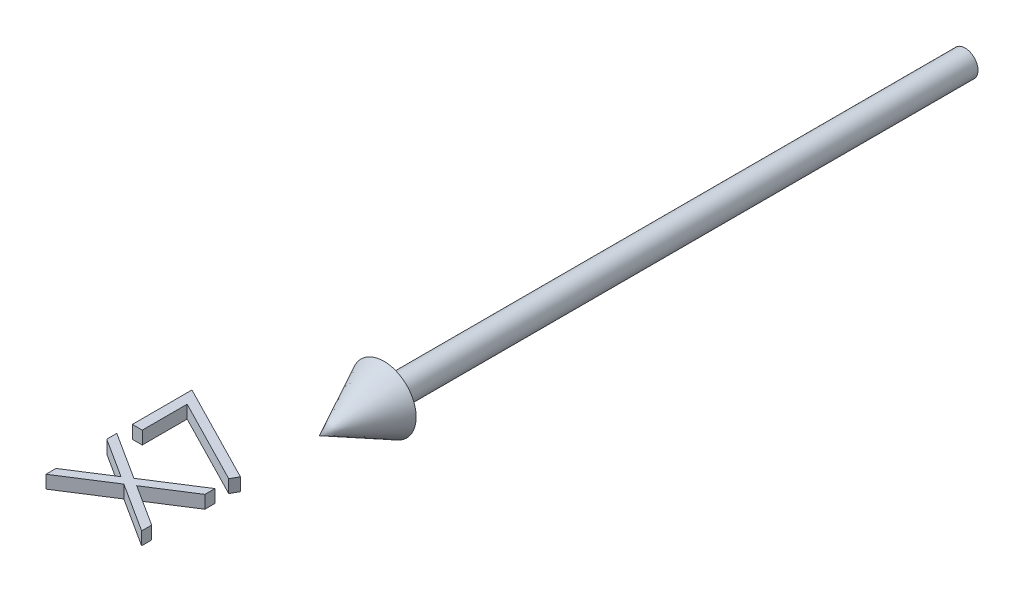
SolidWorks part; units mm, degrees
ref_plane "Front Plane" through (0, 0, 0) normal (0, 0, 1) x (1, 0, 0)
ref_plane "Top Plane" through (0, 0, 0) normal (0, 1, 0) x (1, 0, 0)
ref_plane "Right Plane" through (0, 0, 0) normal (1, 0, 0) x (0, 0, -1)
sketch "Sketch2" plane through (0, 0, 0) normal (0, 1, 0) x (1, 0, 0)
  line L0 (0, 41.95) -> (0, -114.4521) construction
  line L1 (-36.8894, 0) -> (41.4965, 0) construction
  line L2 (0, -100) -> (5, -90)
  line L3 (5, -90) -> (2, -90)
  line L4 (2, -90) -> (2, 0)
  line L5 (2, 0) -> (0, 0)
  line L6 (0, 0) -> (0, -100)
  dimension "D1" = 100
  dimension "D2" = 2
  dimension "D3" = 10
  dimension "D4" = 5
revolve "Revolve1" add sketch "Sketch2" angle 360 about L0
sketch "Sketch3" plane through (0, 0, 0) normal (0, 1, 0) x (1, 0, 0)
  line L0 (0, -103.9528) -> (0, -147.2622) construction
  line L1 (-18.6107, -118.3811) -> (18.3141, -118.3811) construction
  text T0 "X7\r\n\r\n\r\n" font "Century Gothic" height 15
extrude "Boss-Extrude1" add sketch "Sketch3" against normal blind 1 and the other way blind 1 separate body
equation "\"frame_arrow_length\"=100"
equation "\"D1@Sketch2\"=\"frame_arrow_length\""
equation "\"frame_arrow_odA\"=4"
equation "\"D2@Sketch2\"=\"frame_arrow_odA\"/2"
equation "\"frame_arrow_head_od\"=5"
equation "\"D4@Sketch2\"=\"frame_arrow_head_od\""
equation "\"frame_arrow_head_length\"=10"
equation "\"D3@Sketch2\"=\"frame_arrow_head_length\""
equation "\"tvarobot_theta1\"=30"
equation "\"link0_ringA_odA\"= 40"
equation "\"link0_ringA_odB\"= 25"
equation "\"link0_ringA_id\"= 20"
equation "\"link0_ringA_thickness\"= (\"link0_ringA_odB\" - \"link0_ringA_id\")/2"
equation "\"link0_ringA_height\"= 3"
equation "\"link0_ringA_heightA\"= 1.5"
equation "\"link0_ringA_heightB\"=\"link0_ringA_height\"-\"link0_ringA_heightA\""
equation "\"link0_ringB_odA\"= 40"
equation "\"link0_ringB_odB\"= 29"
equation "\"link0_ringB_id\"= \"link0_shaftA_bearing_id\"+1"
equation "\"link0_ringB_thickness\"= (\"link0_ringB_odB\" - \"link0_ringB_id\")/2"
equation "\"link0_ringB_height\"= 3"
equation "\"link0_ringB_heightA\"= 1.5"
equation "\"link0_ringB_heightB\"=\"link0_ringB_height\"-\"link0_ringB_heightA\""
equation "\"link0_shaftA_bearing_od\"=27"
equation "\"link0_shaftA_bearing_id\"=20"
equation "\"link0_shaftA_thrust_bearing_od\"=35"
equation "\"link0_shaftA_thrust_bearing_id\"=20.04"
equation "\"link0_shaftA_retaining_ring_id\"=18.5"
equation "\"link0_shaftA_retaining_ring_groove_width\"=1.5"
equation "\"link0_shaftA_spline_length\"=8.0"
equation "\"link0_shaftA_spline_depth\"=1.0"
equation "\"link0_shaftA_spline_width\"=4.0"
equation "\"link0_shaftA_odA\"=\"link0_shaftA_bearing_id\""
equation "\"link0_shaftA_odB\"=35"
equation "\"link0_shaftA_odC\"=\"link0_shaftA_bearing_id\""
equation "\"link0_shaftA_odD\"=\"link0_shaftA_odC\"-2*\"link0_shaftA_spline_depth\""
equation "\"link0_shaftA_odE\"=\"link0_shaftA_bearing_id\""
equation "\"link0_shaftA_odF\"=\"link0_shaftA_odE\"-2*\"link0_shaftA_spline_depth\""
equation "\"link0_shaftA_idA\"=10"
equation "\"link0_shaftA_idB\"=6"
equation "\"link0_shaftA_length\"=39.5"
equation "\"link0_shaftA_lengthA\"=8.0"
equation "\"link0_shaftA_lengthB\"=12.0"
equation "\"link0_shaftA_lengthC\"=35.0"
equation "\"link0_shaftA_lengthD\"=39.0"
equation "\"link0_shaftA_lengthE\"=\"link0_shaftA_length\"-\"link0_shaftA_lengthD\""
equation "\"link0_shaftA_offsetX\"=11"
equation "\"link0_shaftA_offsetY\"=0"
equation "\"link0_shaftA_bolt_pattern_dia\"=14"
equation "\"link0_motor_center_dist\"=26"
equation "\"link0_46t_pulley_spline_length\"=8"
equation "\"link0_46t_pulley_spline_depth\"=\"link0_shaftA_spline_depth\"*1.025"
equation "\"link0_46t_pulley_spline_width\"=\"link0_shaftA_spline_width\"*1.05"
equation "\"link0_46t_pulley_idA\"=\"link0_shaftA_bearing_id\"*1.025"
equation "\"link0_46t_pulley_idB\"=\"link0_46t_pulley_idA\"-2*\"link0_46t_pulley_spline_depth\""
equation "\"link0_shaftB_spline_length\"=10"
equation "\"link0_shaftB_spline_depth\"=1.0"
equation "\"link0_shaftB_spline_width\"=1.25"
equation "\"link0_shaftB_length\"=7"
equation "\"link0_shaftB_lengthA\"=1.5"
equation "\"link0_shaftB_lengthB\"=2.75"
equation "\"link0_shaftB_odA\"=32"
equation "\"link0_shaftB_odB\"=22"
equation "\"link0_shaftB_odC\"=20"
equation "\"link0_shaftB_idA\"=10"
equation "\"link0_shaftB_bolt_diameter\"=19"
equation "\"link0_shaftB_bearing_od\"=27"
equation "\"link0_shaftB_bearing_id\"=20"
equation "\"link0_motor_length\"=46.5"
equation "\"link0_motor_width\"=28.5"
equation "\"link0_motor_height\"=34"
equation "\"link0_motor_offset\"=8"
equation "\"link0_shellA_thickness\"=2.5"
equation "\"link0_shellB_thickness\"=\"link0_shellA_thickness\""
equation "\"link0_plateA_shellA_height\"=48"
equation "\"link0_shellA_width\" =\"link0_plateA_width\""
equation "\"link0_shellA_height\" = \"link0_plateA_shellA_height\"-\"link0_plateA_height\""
equation "\"link0_shellA_length\" = \"link0_plateA_lengthB\" "
equation "\"link0_shellB_length\"=\"link0_shellA_length\""
equation "\"link0_shellA_radius\" = 0.375*25.4"
equation "\"link0_shellA_radiusA\"= \"link0_plateA_radiusA\""
equation "\"link0_shellA_radiusB\"= \"link0_plateA_radiusB\""
equation "\"link0_shellA_radiusC\"= 3"
equation "\"link0_postA_height\"=7"
equation "\"link0_postA_width\"=16"
equation "\"link0_postA_length\"=20"
equation "\"link0_postA_posX\"=22"
equation "\"link0_postA_posY\"=17.5"
equation "\"link0_postA_pocket_width\"=6.0"
equation "\"link0_postA_pocket_length\"=2.5"
equation "\"link0_postA_pocket_depth\"=9"
equation "\"link0_postA_pocket_posZ\"=10"
equation "\"link0_postB_height\"=7"
equation "\"link0_postB_width\"=16"
equation "\"link0_postB_length\"=20"
equation "\"link0_postB_posX\"=22"
equation "\"link0_postB_posY\"=17.5"
equation "\"link0_postB_id\"=3.0"
equation "\"link0_postB_pocket_width\"=6.0"
equation "\"link0_postB_pocket_length\"=2.5"
equation "\"link0_postB_pocket_depth\"=9"
equation "\"link0_postB_pocket_posZ\"=10"
equation "\"link0_postC_height\"=7"
equation "\"link0_postC_width\"=16"
equation "\"link0_postC_length\"=20"
equation "\"link0_postC_posX\"=22"
equation "\"link0_postC_posY\"=17.5"
equation "\"link0_postC_id\"=3.0"
equation "\"link0_postC_pocket_width\"=6.0"
equation "\"link0_postC_pocket_length\"=2.5"
equation "\"link0_postC_pocket_depth\"=9"
equation "\"link0_postC_pocket_posZ\"=10"
equation "\"link0_postD_height\"=7"
equation "\"link0_postD_width\"=16"
equation "\"link0_postD_length\"=20"
equation "\"link0_postD_posX\"=22"
equation "\"link0_postD_posY\"=17.5"
equation "\"link0_postD_id\"=3.0"
equation "\"link0_postD_pocket_width\"=6.0"
equation "\"link0_postD_pocket_length\"=3.0"
equation "\"link0_postD_pocket_depth\"=9"
equation "\"link0_postD_pocket_posZ\"=10"
equation "\"link0_postE_height\"=5"
equation "\"link0_postE_width\"=16"
equation "\"link0_postE_length\"=\"link0_plateE_lengthA\"-\"link0_lip_height\""
equation "\"link0_postE_posZ\"=22"
equation "\"link0_postE_posX\"=17.5"
equation "\"link0_postE_posY\"=22"
equation "\"link0_postE_id\"=3.0"
equation "\"link0_postE_cbore_id\"=6.5"
equation "\"link0_postE_hole_id\"=3"
equation "\"link0_postF_posZ\"=22"
equation "\"link0_postF_posX\"=17.5"
equation "\"link0_postF_posY\"=\"link0_plateB_lengthA\"+4"
equation "\"link0_postF_id\"=3.0"
equation "\"link0_postF_cbore_id\"=6.5"
equation "\"link0_postF_hole_id\"=3"
equation "\"link0_postG_posZ\"=22"
equation "\"link0_postG_posX\"=17.5"
equation "\"link0_postG_posY\"=\"link0_plateB_lengthA\"+12"
equation "\"link0_postG_id\"=3.0"
equation "\"link0_postG_cbore_id\"=6.5"
equation "\"link0_postG_hole_id\"=3"
equation "\"link0_postHIJ_posY\"=6"
equation "\"link0_postH_posX\"=28"
equation "\"link0_postH_posY\"=20"
equation "\"link0_postH_posZ\"=20"
equation "\"link0_postH_length\"=10"
equation "\"link0_postI_posX\"=28"
equation "\"link0_postI_posY\"=20"
equation "\"link0_postI_posZ\"=135"
equation "\"link0_postI_length\"=10"
equation "\"link0_postJ_posX\"=28"
equation "\"link0_postJ_posY\"=20"
equation "\"link0_postJ_posZ\"=175"
equation "\"link0_postJ_length\"=10"
equation "\"link0_postK_posX\"=28"
equation "\"link0_postK_posY\"=20"
equation "\"link0_postK_posZ\"=175"
equation "\"link0_postK_length\"=10"
equation "\"link0_postL_posX\"=28"
equation "\"link0_postL_posY\"=20"
equation "\"link0_postL_posZ\"=135"
equation "\"link0_postL_length\"=10"
equation "\"link0_postM_posX\"=28"
equation "\"link0_postM_posY\"=20"
equation "\"link0_postM_posZ\"=35"
equation "\"link0_postM_length\"=10"
equation "\"link0_plateA_lengthA\"=30"
equation "\"link0_plateA_lengthB\"=150"
equation "\"link0_plateA_lengthC\"=30"
equation "\"link0_plateA_length\"=\"link0_plateA_lengthA\"+\"link0_plateA_lengthB\"+\"link0_plateA_lengthC\""
equation "\"link0_plateA_width\"=  68"
equation "\"link0_plateA_height\"= \"link0_plateA_radiusA\""
equation "\"link0_plateA_thickness\"=\"link0_shellA_thickness\""
equation "\"link0_plateA_radius\"= 9.5"
equation "\"link0_plateA_radiusA\"= 18"
equation "\"link0_plateA_radiusB\"= 18"
equation "\"link0_plateA_radiusC\"= 3"
equation "\"link0_plateB_length\"= 40"
equation "\"link0_plateB_width\"= \"link0_plateA_width\"*1.005"
equation "\"link0_plateB_height\"= \"link0_plateA_shellA_height\"*1.005"
equation "\"link0_plateB_lengthA\"=\"link0_lip_height\"+\"link0_plateD_thickness\"+\"link0_motor_mount_thickness\""
equation "\"link0_plateB_lengthB\"=\"link0_plateB_height\"-\"link0_plateB_lengthA\""
equation "\"link0_plateB_radiusA\"= \"link0_plateA_radiusA\""
equation "\"link0_plateB_radiusB\"= \"link0_plateA_radiusB\""
equation "\"link0_plateB_radiusC\"= 3"
equation "\"link0_plateB_idA\"=\"link0_shaftA_odC\"+1"
equation "\"link0_plateB_idB\"=\"link0_shaftA_bearing_od\"-2"
equation "\"link0_plateB_idC\"=\"link0_shaftA_bearing_od\"*1.005"
equation "\"link0_plateB_idD\"=\"link0_shaftA_thrust_bearing_od\"+1 "
equation "\"link0_plateB_depthA\"=1.0"
equation "\"link0_plateB_depthB\"=2.0"
equation "\"link0_plateB_depthC\"=8"
equation "\"link0_plateB_depthD\"=\"link0_plateB_length\"-\"link0_lip_height\"-\"link0_plateD_thickness\" "
equation "\"link0_plateC_length\"=\"link0_plateB_length\""
equation "\"link0_plateC_width\"= \"link0_plateB_width\""
equation "\"link0_plateC_height\"= .1*25.4"
equation "\"link0_plateA_hole_od\" = 0.1*25.4"
equation "\"link0_plateA_hole_delx\" = 0.5*25.4"
equation "\"link0_plateA_hole_delz\" = 0.75*25.4"
equation "\"link0_plateA_hole_offx\" = 0.0*25.4"
equation "\"link0_plateA_hole_offz\" = \"link0_plateA_length\"/2"
equation "\"link0_plateB_hole_od\" = 0.1*25.4"
equation "\"link0_plateB_hole_delx\"= 0.75*25.4"
equation "\"link0_plateB_hole_delz\"= 0.75*25.4"
equation "\"link0_plateB_hole_offx\"= 0.0*25.4"
equation "\"link0_plateB_hole_offz\"= 0.0*25.4"
equation "\"link0_plateC_hole_od\"= 0.1*25.4"
equation "\"link0_plateC_hole_delx\"= 0.75*25.4"
equation "\"link0_plateC_hole_delz\"= 0.75*25.4"
equation "\"link0_plateC_hole_offx\"= 0.0*25.4"
equation "\"link0_plateC_hole_offz\"= 0.0*25.4"
equation "\"link0_plateD_height\"=\"link0_plateB_height\"-2*\"link0_shellA_thickness\""
equation "\"link0_plateD_width\"=\"link0_plateB_width\"-2*\"link0_shellA_thickness\""
equation "\"link0_plateD_thickness\"=10"
equation "\"link0_plateD_radiusA\"=\"link0_plateB_radiusA\"-\"link0_shellA_thickness\""
equation "\"link0_plateD_odA\"= .375*25.4"
equation "\"link0_plateD_odB\"= .375*25.4"
equation "\"link0_plateD_bearing_id\"=20"
equation "\"link0_plateD_bearing_od\"=27"
equation "\"link0_plateE_radiusA\"=\"link0_plateA_radiusA\""
equation "\"link0_plateE_radiusB\"=\"link0_plateA_radiusB\""
equation "\"link0_plateE_radiusC\"=8.0"
equation "\"link0_plateE_length\"=30"
equation "\"link0_plateE_lengthA\"=16"
equation "\"link0_plateE_height\"=\"link0_plateB_height\""
equation "\"link0_plateE_width\"=\"link0_plateB_width\""
equation "\"link0_plateE_odA\"=\"gantry_coupler_id\"*0.99"
equation "\"link0_plateE_idA\"=\"link0_plateE_odA\"-20.0"
equation "\"link0_plateE_spline_depth\"=\"link0_poleA_spline_depth\"*1.05"
equation "\"link0_plateE_spline_width\"=\"link0_poleA_spline_width\"*1.075"
equation "\"link0_plateE_spline_length\"=\"link0_poleA_spline_length\""
equation "\"link0_plateE_coupler_length\"=46"
equation "\"link0_lip_height\"=5.0"
equation "\"link0_lip_thickness\"=2.0"
equation "\"link0_motor_mount_thickness\"=8.0"
equation "\"link0_motor_mount_idA\"=22"
equation "\"link0_motor_mount_idB\"=\"link0_shaftB_bearing_od\"*1.005"
equation "\"link0_motor_mount_idC\"=\"link0_shaftB_bearing_od\"-2"
equation "\"link0_motor_mount_depthA\"=5.5"
equation "\"link0_motor_mount_height\"=\"link0_plateD_height\""
equation "\"link0_motor_mount_width\"=\"link0_plateD_width\""
equation "\"link0_motor_mountL_height\"=36"
equation "\"link0_motor_mountL_heightA\"=12"
equation "\"link0_motor_mountL_length\"=50"
equation "\"link0_motor_mountL_lengthA\"=36"
equation "\"gantry_coupler_od\"=25.4*2.0"
equation "\"gantry_coupler_id\"=1.645*25.4"
equation "\"gantry_coupler_offsetX\"=\"link0_plateE_width\"/2"
equation "\"link0_poleA_odA\"=20"
equation "\"link0_poleA_odB\"=36"
equation "\"link0_poleA_idA\"=\"link0_poleA_odA\"-2*\"link0_poleA_thickness\""
equation "\"link0_poleA_idB\"=(\"link0_plateE_idA\"/2+1.5*\"link0_lip_thickness\")*1.04"
equation "\"link0_poleA_thickness\"=3.5"
equation "\"link0_poleA_length\"=100"
equation "\"link0_poleA_lengthA\"=18.5"
equation "\"link0_poleA_lengthB\"=80"
equation "\"link0_poleA_gasket_thickness\"=1.5"
equation "\"link0_poleA_spline_depth\"=1.0"
equation "\"link0_poleA_spline_width\"=4.0"
equation "\"link0_poleA_spline_length\"=10.0"
equation "\"link1_plateB_length\"=30"
equation "\"link1_lip_height\"=\"link0_lip_height\""
equation "\"link0_tension_plateA_width\"=12"
equation "\"link0_tension_plateA_lengthA\"=10.5"
equation "\"link0_tension_plateB_width\"=\"link0_tension_plateA_width\""
equation "\"link0_tension_plateB_lengthA\"=\"link0_tension_plateA_lengthA\""
equation "\"link0_tension_wheelA_posZ\"=7"
equation "\"link0_tension_wheelA_posX\"=\"link0_plateD_height\"/2-\"link0_tension_plateA_lengthA\""
equation "\"link0_m2_clear_hole_id\"=2.35"
equation "\"link0_m2_insert_hole_id\"=2.5"
equation "\"link0_m2_tap_hole_id\"=1.75"
equation "\"link0_m2_nut_socket_width\"=4.25"
equation "\"link0_m2_nut_socket_depth\"=2.5"
equation "\"link0_m2_cbore_id\"=3.75"
equation "\"link0_m2_cbore_depth\"=7"
equation "\"link0_m2_5_clear_hole_id\"=2.75"
equation "\"link0_m2_5_insert_hole_id\"=2.75"
equation "\"link0_m2_5_tap_hole_id\"=2.25"
equation "\"link0_m2_5_nut_socket_width\"=5.25"
equation "\"link0_m2_5_nut_socket_depth\"=2.5"
equation "\"link0_m2_5_cbore_id\"=4.75"
equation "\"link0_m2_5_cbore_depth\"=2.5"
equation "\"link0_m2_5_insert_access_length\"=6.0"
equation "\"link0_m2_5_insert_access_width\"=3.0"
equation "\"link0_m3_clear_hole_id\"=3.25"
equation "\"link0_m3_insert_hole_id\"=3"
equation "\"link0_m3_tap_hole_id\"=2.75"
equation "\"link0_m3_nut_socket_width\"=5.75"
equation "\"link0_m3_nut_socket_depth\"=4.0"
equation "\"link0_m3_cbore_id\"=5.75"
equation "\"link0_m3_cbore_depth\"=3.5"
equation "\"link0_m3_insert_access_length\"=4.5"
equation "\"link0_m3_insert_access_width\"=3.5"
equation "\"link0_rpi_mount_height\"=6"
equation "\"link0_rpi_mount_width\"=49"
equation "\"link0_rpi_mount_length\"=58"
equation "\"link0_rpi_mount_post_od\"=6"
equation "\"link0_rpi_mount_posZ\"=72"
equation "\"link0_rpi_mount_posX\"=11.5"
equation "\"link0_mcu_mount_height\"=5"
equation "\"link0_mcu_mount_width\"=49"
equation "\"link0_mcu_mount_length\"=58"
equation "\"link0_mcu_mount_post_od\"=6"
equation "\"link0_mcu_mount_posZ\"=164"
equation "\"link0_mcu_mount_posX\"=4"
equation "\"link0_pwr_mount_height\"=4"
equation "\"link0_pwr_mount_width\"=15.75"
equation "\"link0_pwr_mount_length\"=75.75"
equation "\"link0_pwr_mount_post_od\"=6"
equation "\"link0_pwr_mount_posZ\"=75"
equation "\"link0_pwr_mount_posX\"=16"
equation "\"link0_pwr_board_height\"=6"
equation "\"link0_pwr_board_width\"=21"
equation "\"link0_pwr_board_length\"=80"
